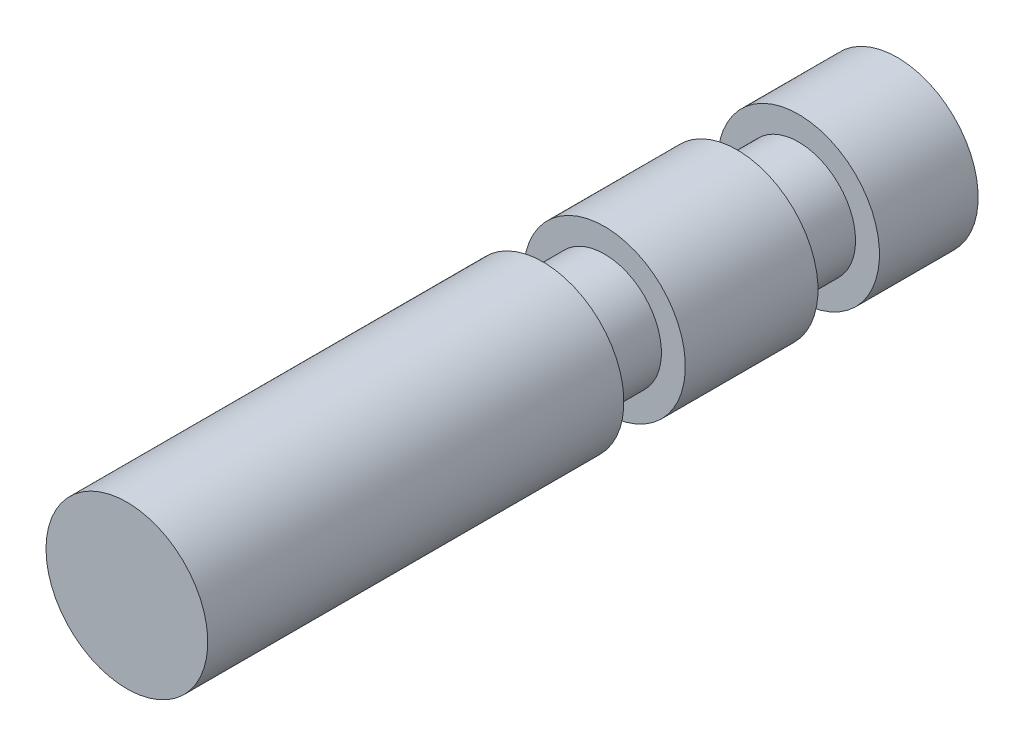
SolidWorks part; units mm, degrees
material "AISI 1015 Steel, Cold Drawn (SS)"
ref_plane "Front Plane" through (0, 0, 0) normal (0, 0, 1) x (1, 0, 0)
ref_plane "Top Plane" through (0, 0, 0) normal (0, 1, 0) x (1, 0, 0)
ref_plane "Right Plane" through (0, 0, 0) normal (1, 0, 0) x (0, 0, -1)
sketch "Sketch1" plane through (0, 0, 0) normal (0, 0, 1) x (1, 0, 0)
  circle A0 centre (0, 0) radius 3.175
  dimension "D1" = 6.35
extrude "Boss-Extrude1" add sketch "Sketch1" along normal blind 30.2387
sketch "Sketch3" plane through (0, 0, 0) normal (0, 1, 0) x (1, 0, 0)
  circle A0 centre (0, -3.175) radius 1.397
  dimension "D1" = 2.794
  dimension "D2" = 3.175
extrude "Cut-Extrude1" [suppressed] cut sketch "Sketch3" against normal through all and the other way through all
sketch "Sketch4" plane through (0, 0, 0) normal (1, 0, 0) x (0, 0, -1)
  line L0 (0, 0) -> (-30.2387, 0) construction
  line L1 (-5.08, 0) -> (-5.08, 2.9464) construction
  line L3 (-6.2865, 3.6576) -> (-3.8735, 3.6576)
  line L4 (-30.2387, 3.175) -> (-30.2387, -3.175) construction
  line L5 (-6.2865, 3.6576) -> (-6.2865, 2.2352)
  line L6 (-6.2865, 2.2352) -> (-3.8735, 2.2352)
  line L7 (-3.8735, 3.6576) -> (-3.8735, 2.2352)
  line L8 (-6.2865, 3.6576) -> (-3.8735, 2.2352) construction
  line L9 (-6.2865, 2.2352) -> (-3.8735, 3.6576) construction
  point P3 (-5.08, 0)
  point P11 (-5.08, 0)
  dimension "D3" = 2.413
  dimension "D1" = 5.08
  dimension "D2" = 2.2352
  dimension "D4" = 1.4224
  dimension "D5" = 3.6576
sketch "Sketch6" plane through (0, 0, 0) normal (0, 0, -1) x (-1, 0, 0)
  circle A0 centre (0, 0) radius 0.635
  dimension "D1" = 1.27
extrude "Cut-Extrude2" [suppressed] cut sketch "Sketch6" against normal up to surface (35.56 mm away) up to face at (3.175, 0, 30.2387)
sketch "Sketch9" plane through (0, 0, 0) normal (0, 0, -1) x (-1, 0, 0)
  circle A0 centre (0, 0) radius 1.397
extrude "Cut-Extrude3" cut sketch "Sketch9" against normal blind 7.62
revolve "Cut-Revolve1" cut sketch "Sketch4" angle 360 about L0
pattern_linear "LPattern1" count 2 spacing 7.62 along (0, 0, 1) of "Cut-Revolve1"
equation "\"D1@Boss-Extrude1\"=0.125+0.5 +0.1 + 0.35 -0.2+ 0.0625"
equation "\"D2@Sketch4\"=0.176/2"
